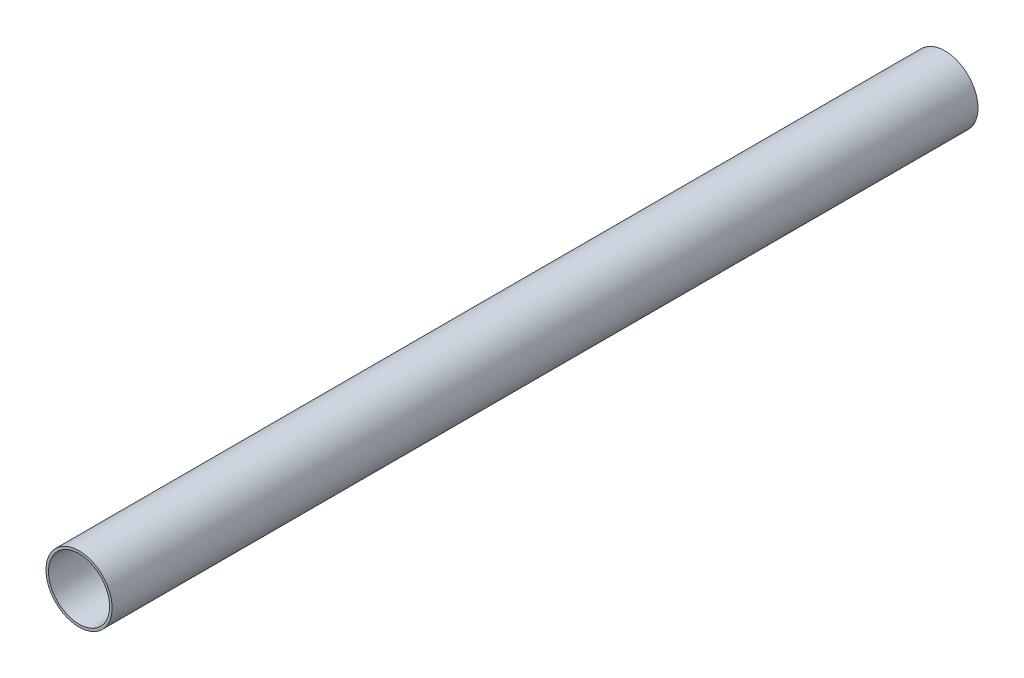
SolidWorks part; units mm, degrees
ref_plane "Front" through (0, 0, 0) normal (0, 0, 1) x (1, 0, 0)
ref_plane "Top" through (0, 0, 0) normal (0, 1, 0) x (1, 0, 0)
ref_plane "Right" through (0, 0, 0) normal (1, 0, 0) x (0, 0, -1)
sketch "Sketch1" plane through (0, 0, 0) normal (0, 0, 1) x (1, 0, 0)
  circle A0 centre (0, 0) radius 19.05
  circle A1 centre (0, 0) radius 20.6375
extrude "Extrude1" add sketch "Sketch1" along normal blind 540
